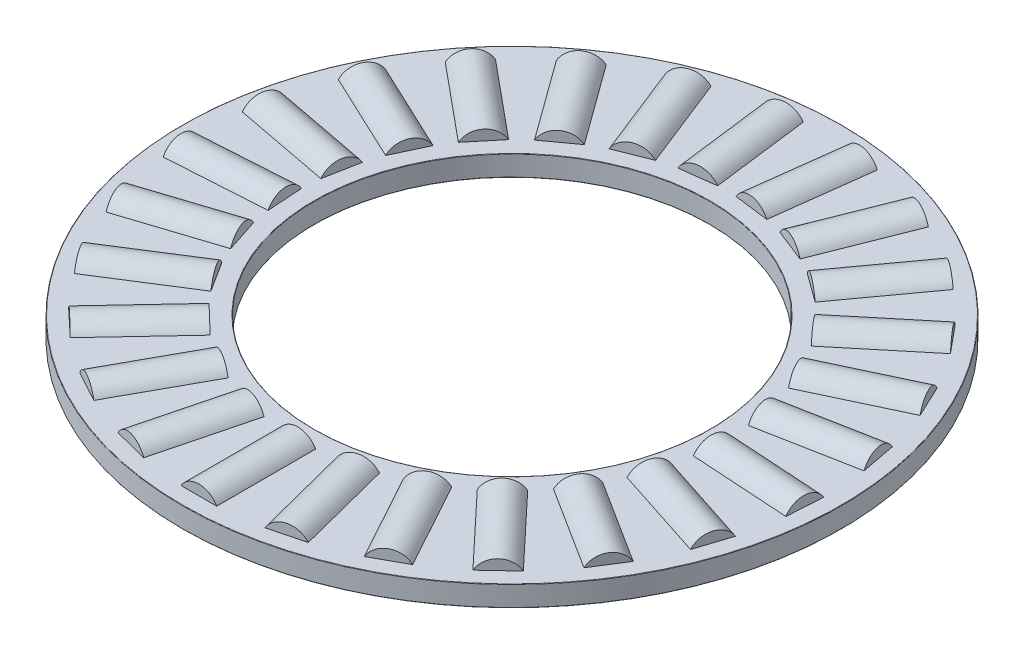
SolidWorks part; units mm, degrees
ref_plane "Front Plane" through (0, 0, 0) normal (0, 0, 1) x (1, 0, 0)
ref_plane "Top Plane" through (0, 0, 0) normal (0, 1, 0) x (1, 0, 0)
ref_plane "Right Plane" through (0, 0, 0) normal (1, 0, 0) x (0, 0, -1)
sketch "Sketch1" plane through (0, 0, 0) normal (1, 0, 0) x (0, 0, -1)
  line L0 (-15.875, 0) -> (15.875, 0) construction
  line L1 (0, -0.9922) -> (0, 0.9922) construction
  line L2 (-15.875, 0.4961) -> (-9.525, 0.4961)
  line L3 (-15.875, 0.4961) -> (-15.875, -0.4961)
  line L4 (-15.875, -0.4961) -> (-9.525, -0.4961)
  line L5 (-9.525, 0.4961) -> (-9.525, -0.4961)
  line L7 (-12.7, 0.9922) -> (-12.7, 0.4961) construction
  line L8 (-15.0813, 0.9922) -> (-10.3188, 0.9922) construction
  line L9 (-15.0813, 0.9922) -> (-15.0813, -0.9922) construction
  line L10 (-15.0813, -0.9922) -> (-10.3188, -0.9922) construction
  line L11 (-10.3188, 0.9922) -> (-10.3188, -0.9922) construction
  point P16 (-15.0813, 0)
revolve "Revolve1" add sketch "Sketch1" angle 360 about L1
sketch "Sketch3" plane through (0, 0, 0) normal (1, 0, 0) x (0, 0, -1)
  line L0 (-15.0813, 0.9922) -> (-15.0813, -0.9922) construction
  line L1 (-15.0813, 0) -> (-10.3188, 0)
  line L2 (-15.0813, 0) -> (-15.0813, 0.9922)
  line L3 (-15.0813, 0.9922) -> (-10.3188, 0.9922)
  line L4 (-10.3188, 0) -> (-10.3188, 0.9922)
revolve "Cut-Revolve1" cut sketch "Sketch3" angle 360 about L1
sketch "Sketch2" plane through (0, 0, 0) normal (1, 0, 0) x (0, 0, -1)
  line L1 (-15.0813, 0) -> (-10.3188, 0)
  line L2 (-15.0813, 0) -> (-15.0813, 0.9922)
  line L3 (-15.0813, 0.9922) -> (-10.3188, 0.9922)
  line L4 (-10.3188, 0) -> (-10.3188, 0.9922)
revolve "Revolve2" add sketch "Sketch2" angle 360 about L1
ref_axis "Axis1" through (0, 0.9922, 0) along (0, -1, 0)
pattern_circular "CirPattern1" count 25 every 14.4 about axis through (0, 0.9922, 0) along (0, -1, 0) of bodies 187 411
pattern_circular "CirPattern2" count 25 every 14.4 about axis through (0, 0.9922, 0) along (0, -1, 0) of "Cut-Revolve1"
sketch "Sketch4" plane through (0, 0, 0) normal (1, 0, 0) x (0, 0, -1)
  line L0 (-15.875, 0.4961) -> (-15.875, -0.4961) construction
  line L1 (-15.875, 9.1091) -> (-9.525, 9.1091)
  line L2 (-15.875, 9.1091) -> (-15.875, 9.9219)
  line L3 (-15.875, 9.9219) -> (-9.525, 9.9219)
  line L4 (-9.525, 9.1091) -> (-9.525, 9.9219)
  line L5 (-15.875, -9.9219) -> (-9.525, -9.9219)
  line L6 (-15.875, -9.9219) -> (-15.875, -9.1091)
  line L7 (-15.875, -9.1091) -> (-9.525, -9.1091)
  line L8 (-9.525, -9.9219) -> (-9.525, -9.1091)
  line L10 (-9.525, 0.4961) -> (-9.525, -0.4961) construction
  line L11 (0, 0) -> (-15.875, 0) construction
  line L12 (-15.875, 0) -> (15.875, 0) construction
  line L13 (0, -0.9922) -> (0, 0.9922) construction
revolve "Revolve3" [suppressed] add sketch "Sketch4" angle 360 about L1
fillet "Fillet1" [suppressed] radius 0.0198
fillet "Fillet2" radius 0.0198 4 edges at (0, -0.4961, -9.525) (0, 0.4961, -9.525) (0, -0.4961, -15.875) (0, 0.4961, -15.875)
fillet "Fillet3" [suppressed] radius 0.0198
equation "\"D2@Sketch1\" = \"Th@Sketch1\"*.5"
equation "\"D1@Fillet1\" = \"Th@Sketch1\"*.01"
equation "\"D1@Fillet2\" = \"D1@Fillet1\""
equation "\"D1@Fillet3\" = \"D1@Fillet1\""
equation "\"D1@Sketch1\" = \"D3@Sketch1\"*.75"
equation "\"Angle@CirPattern1\" = 360/\"Rollers@CirPattern1\""
equation "\"Rollers@CirPattern1\" = \"OD@Sketch1\"*20"
equation "\"D1@CirPattern2\" = \"Rollers@CirPattern1\""
equation "\"D2@CirPattern2\" = \"Angle@CirPattern1\""
equation "\"Ht@Sketch4\" = \"Th@Sketch1\"*10"
